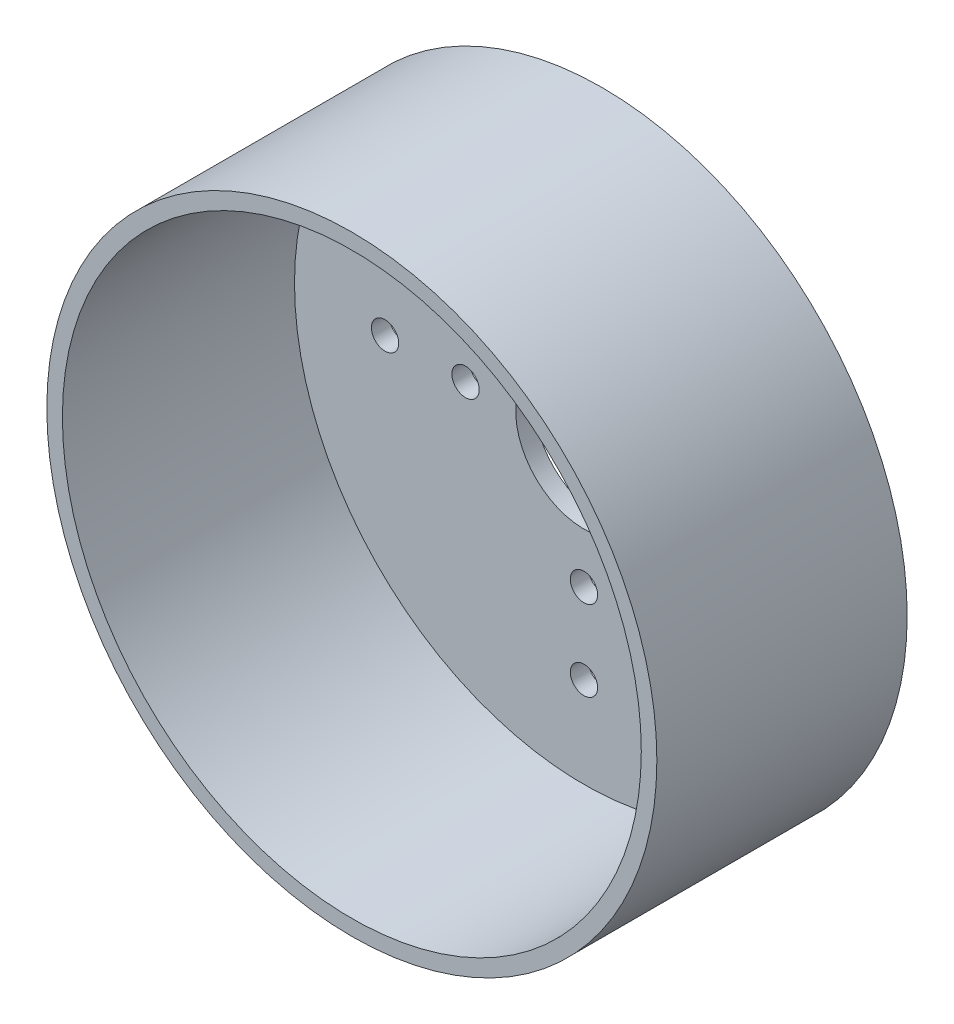
SolidWorks part; units mm, degrees
ref_plane "Front Plane" through (0, 0, 0) normal (0, 0, 1) x (1, 0, 0)
ref_plane "Top Plane" through (0, 0, 0) normal (0, 1, 0) x (1, 0, 0)
ref_plane "Right Plane" through (0, 0, 0) normal (1, 0, 0) x (0, 0, -1)
sketch "Sketch1" plane through (0, 0, 0) normal (0, 0, 1) x (1, 0, 0)
  circle A0 centre (0, 0) radius 31.51
  circle A1 centre (0, 0) radius 33.51
  circle A2 centre (0, 0) radius 31.8
  dimension "D1" = 63.02
  dimension "D2" = 2
extrude "Boss-Extrude1" add sketch "Sketch1" along normal blind 2 contours A1
sketch "Sketch2" plane through (0, 0, 2) normal (0, 0, 1) x (1, 0, 0)
  circle A0 centre (0, 0) radius 31.8
  circle A1 centre (0, 0) radius 33.51
extrude "Boss-Extrude2" add sketch "Sketch2" along normal blind 25.5
sketch "Sketch3" plane through (0, 0, 0) normal (0, 0, -1) x (-1, 0, 0)
  line L0 (0, 0) -> (33.51, 0) construction
  circle A0 centre (0, 0) radius 33.51 construction
  circle A1 centre (21.85, 0) radius 1.5
  circle A2 centre (13.01, 0) radius 1.5
  circle A3 centre (0, -21.85) radius 1.5
  circle A4 centre (0, -13.01) radius 1.5
  circle A5 centre (-21.85, 0) radius 1.5
  circle A6 centre (-13.01, 0) radius 1.5
  circle A7 centre (0, 21.85) radius 1.5
  circle A8 centre (0, 13.01) radius 1.5
  point P25 (0, 0)
  dimension "D1" = 3
  dimension "D2" = 3
  dimension "D3" = 21.85
  dimension "D4" = 13.01
  dimension "D5" = 4
extrude "Cut-Extrude1" cut sketch "Sketch3" against normal through all
sketch "Sketch4" plane through (0, 0, 2) normal (0, 0, 1) x (1, 0, 0)
  circle A0 centre (0, 0) radius 7.5
extrude "Cut-Extrude2" cut sketch "Sketch4" against normal through all
